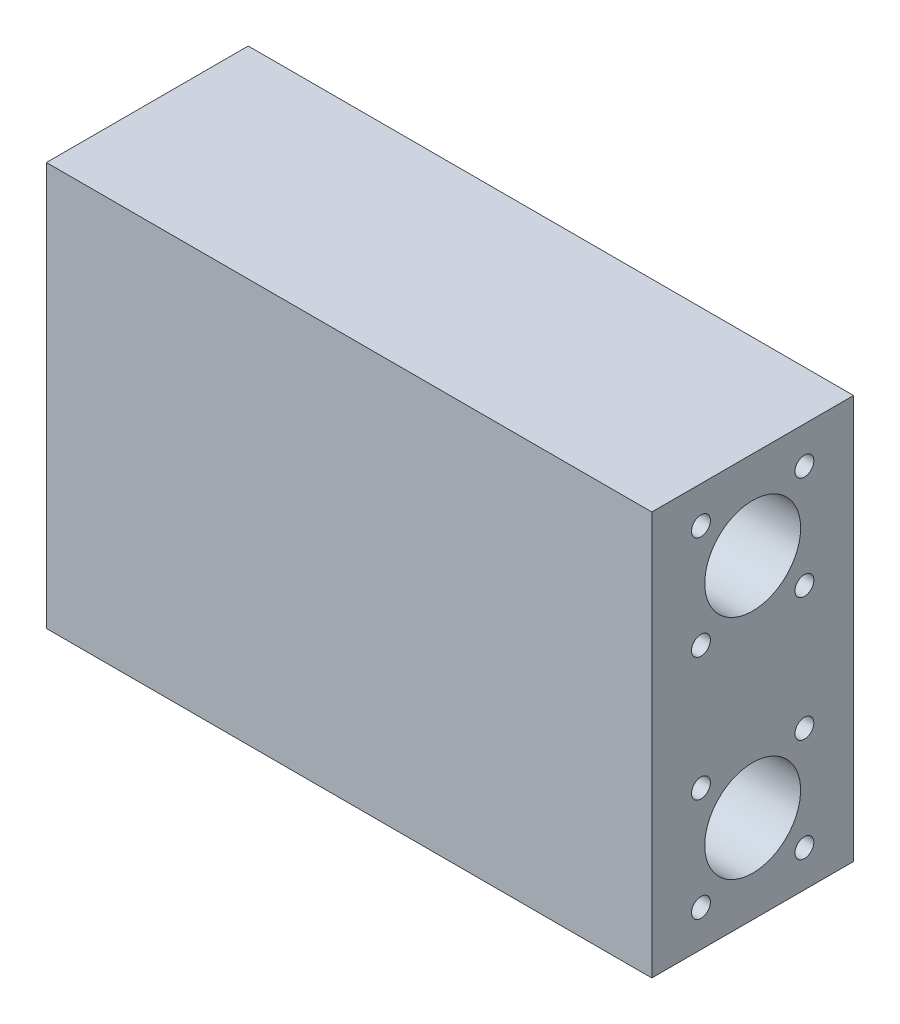
SolidWorks part; units mm, degrees
ref_plane "Front Plane" through (0, 0, 0) normal (0, 0, 1) x (1, 0, 0)
ref_plane "Top Plane" through (0, 0, 0) normal (0, 1, 0) x (1, 0, 0)
ref_plane "Right Plane" through (0, 0, 0) normal (1, 0, 0) x (0, 0, -1)
sketch "Sketch1" plane through (0, 0, 0) normal (0, 0, 1) x (1, 0, 0)
  line L1 (0, 0) -> (120, 0)
  line L2 (0, 0) -> (0, 80)
  line L3 (0, 80) -> (120, 80)
  line L4 (120, 0) -> (120, 80)
  dimension "D1" = 80
  dimension "D2" = 120
extrude "Boss-Extrude1" add sketch "Sketch1" along normal blind 40 contours L3 L4 L1 L2
sketch "Sketch2" plane through (0, 0, 0) normal (-1, 0, 0) x (0, 0, 1)
  line L0 (20, 80) -> (20, 0) construction
  line L1 (40, 80) -> (0, 80) construction
  line L2 (40, 0) -> (0, 0) construction
  line L3 (40, 40) -> (0, 40) construction
  line L4 (40, 0) -> (40, 80) construction
  line L5 (0, 0) -> (0, 80) construction
  line L6 (0, 62.5) -> (40, 62.5) construction
  line L7 (0, 17.5) -> (40, 17.5) construction
  circle A1 centre (30.25, 72.75) radius 1.85
  circle A2 centre (9.75, 72.75) radius 1.85
  circle A3 centre (30.25, 52.25) radius 1.85
  circle A4 centre (9.75, 52.25) radius 1.85
  circle A5 centre (9.75, 27.75) radius 1.85
  circle A6 centre (30.25, 27.75) radius 1.85
  circle A7 centre (30.25, 7.25) radius 1.85
  circle A9 centre (9.75, 7.25) radius 1.85
  dimension "D4" = 3.7
  dimension "D1" = 22.5
  dimension "D2" = 9.75
  dimension "D3" = 7.25
extrude "linear-bearing-screw-cuts" cut sketch "Sketch2" against normal blind 14
sketch "Sketch3" plane through (0, 0, 0) normal (-1, 0, 0) x (0, 0, 1)
  line L0 (20, 80) -> (20, 0) construction
  line L1 (40, 80) -> (0, 80) construction
  line L2 (40, 0) -> (0, 0) construction
  line L3 (0, 40) -> (40, 40) construction
  line L4 (0, 0) -> (0, 80) construction
  line L5 (40, 0) -> (40, 80) construction
  line L6 (0, 62.5) -> (40, 62.5) construction
  line L7 (0, 17.5) -> (40, 17.5) construction
  circle A0 centre (20, 62.5) radius 9.5
  circle A2 centre (20, 17.5) radius 9.5
  dimension "D2" = 19
  dimension "D1" = 45
extrude "linear-bearings-hole" cut sketch "Sketch3" against normal blind 55
sketch "Sketch4" plane through (120, 0, 0) normal (1, 0, 0) x (0, 0, -1)
  line L0 (-20, 80) -> (-20, 0) construction
  line L1 (-40, 80) -> (0, 80) construction
  line L2 (-40, 0) -> (0, 0) construction
  line L3 (-40, 40) -> (0, 40) construction
  line L4 (-40, 0) -> (-40, 80) construction
  line L5 (0, 0) -> (0, 80) construction
  line L6 (-40, 62.5) -> (0, 62.5) construction
  line L7 (-40, 17.5) -> (0, 17.5) construction
  circle A0 centre (-9.75, 72.75) radius 1.875
  circle A1 centre (-30.25, 72.75) radius 1.875
  circle A2 centre (-9.75, 52.25) radius 1.875
  circle A3 centre (-30.25, 52.25) radius 1.875
  circle A4 centre (-30.25, 27.75) radius 1.875
  circle A5 centre (-9.75, 27.75) radius 1.875
  circle A6 centre (-9.75, 7.25) radius 1.875
  circle A7 centre (-30.25, 7.25) radius 1.875
  dimension "D2" = 3.75
  dimension "D1" = 45
  dimension "D3" = 7.25
  dimension "D4" = 9.75
extrude "linear-bearing-screw-cuts2" cut sketch "Sketch4" against normal blind 14
sketch "Sketch5" plane through (120, 0, 0) normal (1, 0, 0) x (0, 0, -1)
  line L0 (-20, 80) -> (-20, 0) construction
  line L1 (-40, 80) -> (0, 80) construction
  line L2 (-40, 0) -> (0, 0) construction
  line L3 (0, 40) -> (-40, 40) construction
  line L4 (0, 0) -> (0, 80) construction
  line L5 (-40, 0) -> (-40, 80) construction
  line L6 (-40, 62.5) -> (0, 62.5) construction
  line L7 (-40, 17.5) -> (0, 17.5) construction
  circle A0 centre (-20, 62.5) radius 9.5
  circle A1 centre (-20, 17.5) radius 9.5
  dimension "D2" = 19
  dimension "D1" = 45
extrude "Cut-Extrude4" cut sketch "Sketch5" against normal blind 55
sketch "Sketch10" plane through (0, 0, 0) normal (0, -1, 0) x (1, 0, 0)
  line L0 (87.5, 40) -> (82.5, 35)
  line L1 (0, 40) -> (120, 40) construction
  line L2 (82.5, 35) -> (97.5, 35)
  line L3 (97.5, 35) -> (92.5, 40)
  line L4 (92.5, 40) -> (87.5, 40)
  line L5 (60, 40) -> (60, 0) construction
  line L6 (0, 0) -> (120, 0) construction
  line L7 (75, 40) -> (75, 0) construction
  line L8 (120, 40) -> (120, 0) construction
  line L9 (52.5, 35) -> (57.5, 40)
  line L10 (67.5, 35) -> (52.5, 35)
  line L11 (62.5, 40) -> (67.5, 35)
  line L12 (57.5, 40) -> (62.5, 40)
  line L13 (22.5, 35) -> (27.5, 40)
  line L14 (37.5, 35) -> (22.5, 35)
  line L15 (32.5, 40) -> (37.5, 35)
  line L16 (27.5, 40) -> (32.5, 40)
  point P12 (90, 40)
  dimension "D1" = 30
  dimension "D2" = 15
  dimension "D3" = 45
  dimension "D4" = 5
  dimension "D5" = 45
  dimension "D6" = 45
extrude "Cut-Extrude8" [suppressed] cut sketch "Sketch10" against normal blind 60
